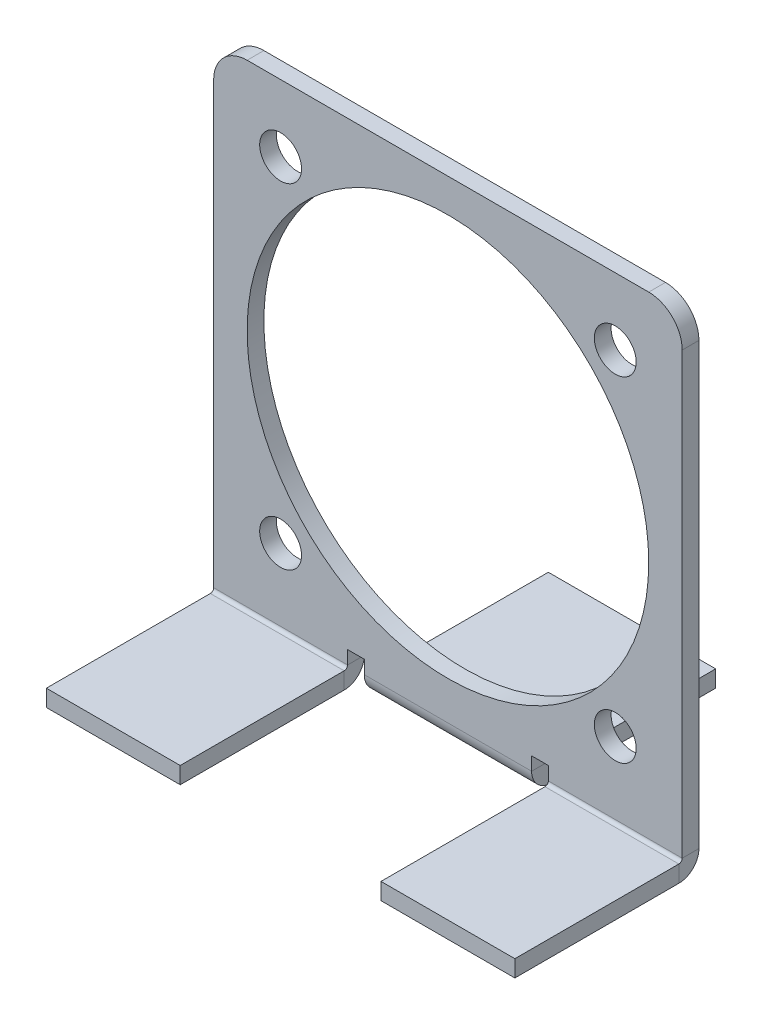
SolidWorks part; units mm, degrees
note: The reader was unsure of these and kept them because the rebuilt part matched: flange length of "Kante-Lasche2", "Kante-Lasche3".
material "2014-T6"
ref_plane "Ebene vorne" through (0, 0, 0) normal (0, 0, 1) x (1, 0, 0)
ref_plane "Ebene oben" through (0, 0, 0) normal (0, 1, 0) x (1, 0, 0)
ref_plane "Ebene rechts" through (0, 0, 0) normal (1, 0, 0) x (0, 0, -1)
sketch "Skizze1" plane through (0, 0, 0) normal (0, 0, 1) x (1, 0, 0)
  line L0 (0, 0) -> (0, 5.5) construction
  line L1 (-14, 29.5) -> (14, 29.5)
  line L2 (-14, 29.5) -> (-14, 0)
  line L3 (-14, 0) -> (14, 0)
  line L4 (14, 29.5) -> (14, 0)
  line L5 (-10, 25.5) -> (10, 25.5) construction
  line L6 (-10, 25.5) -> (-10, 5.5) construction
  line L7 (-10, 5.5) -> (10, 5.5) construction
  line L8 (10, 25.5) -> (10, 5.5) construction
  line L9 (-10, 15.5) -> (10, 15.5) construction
  line L10 (0, 25.5) -> (0, 29.5) construction
  line L12 (-10, 15.5) -> (-14, 15.5) construction
  circle A0 centre (-10, 25.5) radius 1.25
  circle A1 centre (10, 25.5) radius 1.25
  circle A2 centre (10, 5.5) radius 1.25
  circle A3 centre (-10, 5.5) radius 1.25
  circle A4 centre (0, 15.5) radius 12
  dimension "D3" = 2.5
  dimension "D2" = 24
  dimension "D1" = 28
  dimension "D4" = 20
  dimension "D5" = 15.5
base flange "Basis-Blech1" sketch "Skizze1" thickness 1 reverse thickness direction no parameters "D1"=0.2
fillet "Verrundung1" radius 2 2 edges at (-14, 29.5, -0.5) (14, 29.5, -0.5)
sketch "Skizze9" plane through (0, 0, 0) normal (0, 0, 1) x (1, 0, 0)
  line L0 (-14, 0) -> (14, 0) construction
  line L1 (-6, 2) -> (-5, 2)
  line L2 (-6, 2) -> (-6, 0)
  line L3 (-6, 0) -> (-5, 0)
  line L4 (-5, 2) -> (-5, 0)
  line L5 (0, 0) -> (0, 4.9297) construction
  line L6 (5, 2) -> (6, 2)
  line L7 (5, 2) -> (5, 0)
  line L8 (5, 0) -> (6, 0)
  line L9 (6, 2) -> (6, 0)
  dimension "D1" = 1
  dimension "D2" = 10
  dimension "D3" = 2
extrude "Schnitt-Linear austragen1" cut sketch "Skizze9" against normal through all normal cut yes
edge flange "Kante-Lasche2" sketch "Skizze14" flange profiles "Skizze14", "Skizze15" flange angle 90 flange length 10 flange position material inside bend radius 0.2 thickness 1 relief rectangular parameters "D6"=10, "D8"=1
sketch "Skizze14" plane through (0, 0, 0) normal (0, -1, 0) x (1, 0, 0)
  line L2 (-14, 0) -> (-14, 10)
  line L3 (-14, 10) -> (-6, 10)
  line L4 (-6, 10) -> (-6, 0)
  line L5 (-14, 0) -> (-6, 0) construction
  line L6 (-14, 0) -> (-6, 0)
sketch "Skizze15" plane through (0, 0, 0) normal (0, -1, 0) x (1, 0, 0)
  line L2 (6, 0) -> (6, 10)
  line L3 (6, 10) -> (14, 10)
  line L4 (14, 10) -> (14, 0)
  line L5 (6, 0) -> (14, 0) construction
  line L6 (6, 0) -> (14, 0)
bend "Kantenbiegung2" bend radius 0.2 bend angle 90 parameters "D5"=1
bend "Kantenbiegung3" bend radius 0.2 bend angle 90 parameters "D5"=2
edge flange "Kante-Lasche3" sketch "Skizze18" flange angle 90 flange length 10 flange position material inside bend radius 0.2 thickness 1 relief rectangular parameters "D6"=10
sketch "Skizze18" plane through (0, 0, -1) normal (0, -1, 0) x (-1, 0, 0)
  line L2 (-5, 0) -> (-5, 10)
  line L3 (-5, 10) -> (5, 10)
  line L4 (5, 10) -> (5, 0)
  line L5 (5, 0) -> (-5, 0) construction
  line L6 (5, 0) -> (-5, 0)
bend "Kantenbiegung4" bend radius 0.2 bend angle 90 parameters "D5"=3
sketch "Biegung-Linien1" plane through (0, 0, 0) normal (0, 1, 0) x (1, 0, 0)
sketch "Rahmen1" plane through (0, 0, 0) normal (0, 1, 0) x (1, 0, 0)
sheet metal parameters "Blech1" thickness 1 parameters "D1"=0.2
flat pattern "Abwicklung1" [suppressed]
sketch "Biegung-Linien2" plane through (0, 0, 0) normal (0, 1, 0) x (1, 0, 0)
sketch "Rahmen2" [suppressed] plane through (0, 0, 0) normal (0, 1, 0) x (1, 0, 0)
sheet metal parameters "Blech3" thickness 1 parameters "D1"=0.2
flat pattern "Abwicklung1"
sketch "Biegung-Linien2" plane through (0, 0, 0) normal (0, 1, 0) x (1, 0, 0)
sketch "Rahmen2" [suppressed] plane through (0, 0, 0) normal (0, 1, 0) x (1, 0, 0)
sheet metal parameters "Blech4" thickness 1 parameters "D1"=0.2
flat pattern "Abwicklung1" [suppressed]
sketch "Biegung-Linien2" plane through (0, 0, 0) normal (0, 1, 0) x (1, 0, 0)
sketch "Rahmen2" [suppressed] plane through (0, 0, 0) normal (0, 1, 0) x (1, 0, 0)
bend of the flat pattern "Abwickeln-<Kantenbiegung2>1"
bend of the flat pattern "Abwickeln-<Kantenbiegung3>1"
sheet metal parameters "Blech5" thickness 1 parameters "D1"=0.2
flat pattern "Abwicklung1" [suppressed]
sketch "Biegung-Linien2" plane through (0, 0, 0) normal (0, 1, 0) x (1, 0, 0)
sketch "Rahmen2" [suppressed] plane through (0, 0, 0) normal (0, 1, 0) x (1, 0, 0)
bend of the flat pattern "Abwickeln-<Kantenbiegung2>1"
bend of the flat pattern "Abwickeln-<Kantenbiegung3>1"
bend of the flat pattern "Abwickeln-<Kantenbiegung4>1"
